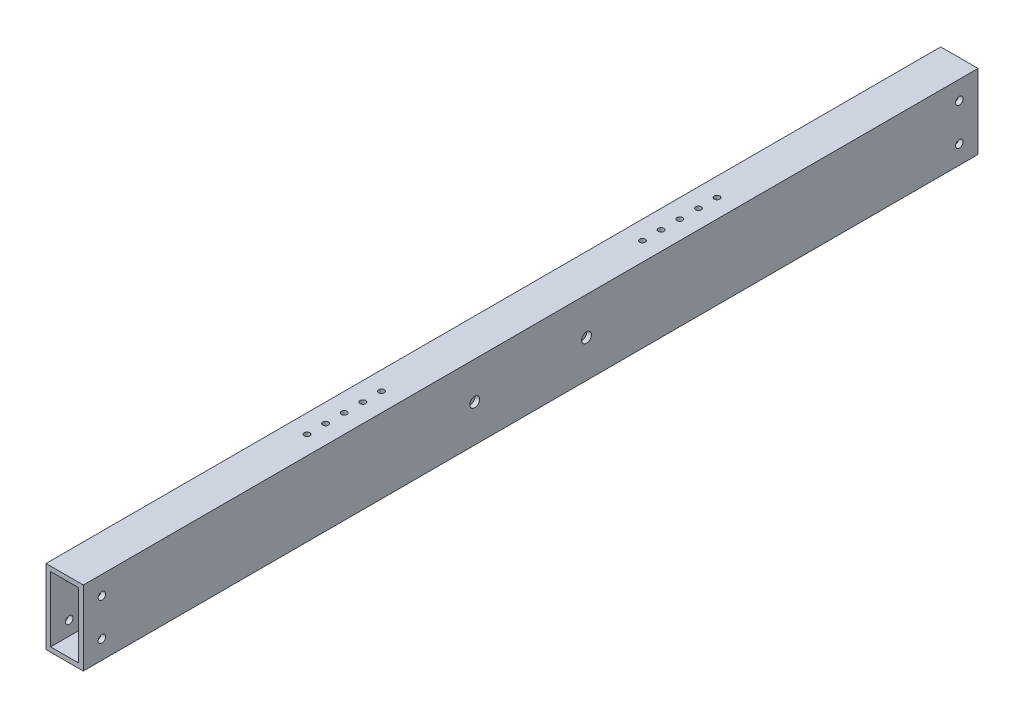
SolidWorks part; units mm, degrees
material "6061-T6 (SS)"
ref_plane "Front Plane" through (0, 0, 0) normal (0, 0, 1) x (1, 0, 0)
ref_plane "Top Plane" through (0, 0, 0) normal (0, 1, 0) x (1, 0, 0)
ref_plane "Right Plane" through (0, 0, 0) normal (1, 0, 0) x (0, 0, -1)
sketch "Sketch1" plane through (0, 0, 0) normal (0, 0, 1) x (1, 0, 0)
  line L0 (-9.525, 22.225) -> (9.525, 22.225)
  line L1 (-12.7, 25.4) -> (12.7, 25.4)
  line L2 (-12.7, 25.4) -> (-12.7, -25.4)
  line L3 (-12.7, -25.4) -> (12.7, -25.4)
  line L4 (12.7, 25.4) -> (12.7, -25.4)
  line L5 (-12.7, 25.4) -> (12.7, -25.4) construction
  line L6 (-12.7, -25.4) -> (12.7, 25.4) construction
  line L7 (9.525, 22.225) -> (9.525, -22.225)
  line L8 (-9.525, -22.225) -> (9.525, -22.225)
  line L9 (-9.525, 22.225) -> (-9.525, -22.225)
  point P0 (0, 0)
  dimension "D1" = 50.8
  dimension "D2" = 25.4
  dimension "D3" = 3.175
extrude "Boss-Extrude1" add sketch "Sketch1" along normal mid plane 609.6
hole_wizard "#10 Clearance Hole1" positions "Sketch4" profile "Sketch3" hole size "#10" standard "ANSI Inch" end condition through all
sketch "Sketch4" plane through (12.7, 0, 0) normal (1, 0, 0) x (0, 0, -1)
  line L0 (-304.8, 25.4) -> (304.8, 25.4) construction
  point P0 (-292.1, 12.7)
  point P13 (-292.1, -12.7)
  dimension "D2" = 12.7
  dimension "D1" = 2
sketch "Sketch3" plane through (12.7, 12.7, 292.1) normal (0, 1, 0) x (0, 0, -1)
  line L0 (0, 0) -> (0, 25.4)
  line L1 (0, 25.4) -> (2.5527, 25.4)
  line L2 (2.5527, 25.4) -> (2.5527, 0)
  line L5 (2.5527, 0) -> (0, 0)
  line L11 (0, -6.35) -> (0, 107.95) construction
  dimension "Thru Hole Dia." = 5.1054
  dimension "Thru Hole Depth" = 25.4
mirror "Mirror1" about plane through (0, 0, 0) normal (0, 0, 1) of "#10 Clearance Hole1"
hole_wizard "1/4 Clearance Hole2" positions "Sketch6" profile "Sketch5" hole size "1/4" standard "ANSI Inch" end condition through all
sketch "Sketch6" plane through (12.7, 0, 0) normal (1, 0, 0) x (0, 0, -1)
  line L0 (-38.1, 0) -> (38.1, 0) construction
  point P0 (-38.1, 0)
  point P2 (38.1, 0)
  dimension "D1" = 76.2
sketch "Sketch5" plane through (12.7, 0, 38.1) normal (0, 1, 0) x (0, 0, -1)
  line L0 (0, 0) -> (0, 25.4)
  line L1 (0, 25.4) -> (3.3782, 25.4)
  line L2 (3.3782, 25.4) -> (3.3782, 0)
  line L5 (3.3782, 0) -> (0, 0)
  line L11 (0, -6.35) -> (0, 107.95) construction
  dimension "Thru Hole Dia." = 6.7564
  dimension "Thru Hole Depth" = 25.4
sketch "Sketch7" plane through (0, 25.4, 0) normal (0, 1, 0) x (1, 0, 0)
  line L0 (-12.7, -304.8) -> (-12.7, 304.8) construction
  line L1 (12.7, 304.8) -> (-12.7, 304.8) construction
  circle A0 centre (0, 139.7) radius 1.905
  circle A1 centre (0, 127) radius 1.905
  circle A2 centre (0, 114.3) radius 1.905
  circle A3 centre (0, 101.6) radius 1.905
  circle A4 centre (0, 88.9) radius 1.905
  dimension "D1" = 3.81
  dimension "D2" = 12.7
  dimension "D3" = 165.1
  dimension "D4" = 5
extrude "Cut-Extrude1" cut sketch "Sketch7" against normal through all
mirror "Mirror2" about plane through (0, 0, 0) normal (0, 0, 1) of "Cut-Extrude1"
